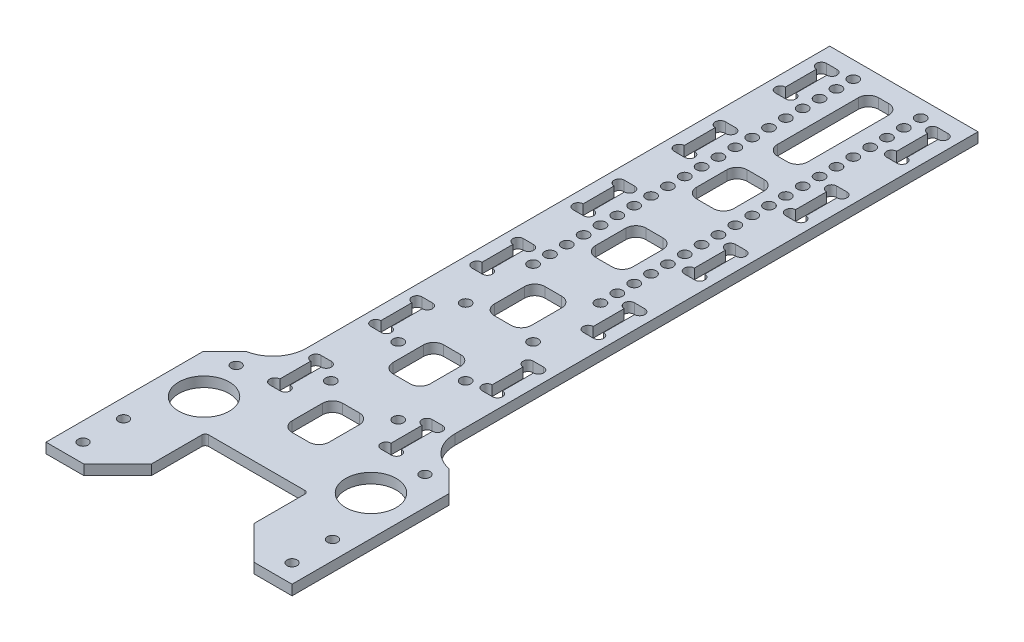
SolidWorks part; units mm, degrees
material "Thornel Mat VMA"
ref_plane "前视基准面" through (0, 0, 0) normal (0, 0, 1) x (1, 0, 0)
ref_plane "上视基准面" through (0, 0, 0) normal (0, 1, 0) x (1, 0, 0)
ref_plane "右视基准面" through (0, 0, 0) normal (1, 0, 0) x (0, 0, -1)
sketch "草图1" plane through (0, 0, 0) normal (0, 1, 0) x (1, 0, 0)
  line L1 (0, 0) -> (80, 0)
  line L2 (0, 0) -> (0, 225)
  line L3 (0, 225) -> (80, 225)
  line L4 (80, 0) -> (80, 225)
  dimension "D1" = 80
  dimension "D2" = 225
extrude "凸台-拉伸1" add sketch "草图1" along normal blind 3
sketch "草图2" plane through (0, 3, 0) normal (0, 1, 0) x (1, 0, 0)
  line L0 (40, 0) -> (40, 225) construction
  line L5 (0, 0) -> (80, 0) construction
  line L6 (80, 225) -> (0, 225) construction
  line L12 (55.25, 33) -> (24.75, 33)
  line L13 (55.25, 33) -> (55.25, 0)
  line L14 (55.25, 0) -> (24.75, 0)
  line L15 (24.75, 33) -> (24.75, 0)
  line L16 (55.25, 33) -> (24.75, 0) construction
  line L17 (55.25, 0) -> (24.75, 33) construction
  point P0 (40, 16.5)
  dimension "D1" = 33
  dimension "D2" = 30.5
extrude "切除-拉伸1" cut sketch "草图2" against normal through all
sketch "草图3" plane through (0, 0, 0) normal (0, -1, 0) x (1, 0, 0)
  line L1 (40, -225) -> (40, -33) construction
  line L2 (80, -225) -> (62, -225)
  line L3 (80, -225) -> (80, -60)
  line L4 (80, -60) -> (62, -60)
  line L5 (62, -225) -> (62, -60)
  line L6 (80, -225) -> (0, -225) construction
  line L7 (55.25, -33) -> (24.75, -33) construction
  line L8 (0, -60) -> (18, -60)
  line L9 (18, -225) -> (18, -60)
  line L10 (0, -225) -> (18, -225)
  line L11 (0, -225) -> (0, -60)
  dimension "D1" = 165
  dimension "D2" = 18
extrude "切除-拉伸2" cut sketch "草图3" against normal blind 3
chamfer "倒角1" distance 10 angle 45 2 edges at (80, 1.5, -60) (0, 1.5, -60)
fillet "圆角1" radius 10 2 edges at (62, 1.5, -60) (18, 1.5, -60)
sketch "草图4" plane through (0, 3, 0) normal (0, 1, 0) x (1, 0, 0)
  line L0 (40, 225) -> (40, 33) construction
  line L1 (62, 225) -> (18, 225) construction
  line L2 (55.25, 33) -> (24.75, 33) construction
  line L3 (18, 225) -> (18, 69.798) construction
  line L4 (21.95, 220.1) -> (25.05, 220.1)
  line L5 (21.95, 220.1) -> (21.95, 204.9)
  line L6 (21.95, 204.9) -> (25.05, 204.9)
  line L7 (25.05, 220.1) -> (25.05, 204.9)
  line L8 (58.05, 204.9) -> (54.95, 204.9)
  line L9 (54.95, 220.1) -> (54.95, 204.9)
  line L10 (58.05, 220.1) -> (54.95, 220.1)
  line L11 (58.05, 220.1) -> (58.05, 204.9)
  line L12 (21.95, 190.1) -> (21.95, 174.9)
  line L13 (21.95, 190.1) -> (25.05, 190.1)
  line L14 (25.05, 190.1) -> (25.05, 174.9)
  line L15 (21.95, 174.9) -> (25.05, 174.9)
  line L16 (58.05, 174.9) -> (54.95, 174.9)
  line L17 (54.95, 190.1) -> (54.95, 174.9)
  line L18 (58.05, 190.1) -> (54.95, 190.1)
  line L19 (58.05, 190.1) -> (58.05, 174.9)
  line L20 (21.95, 160.1) -> (21.95, 144.9)
  line L21 (21.95, 160.1) -> (25.05, 160.1)
  line L22 (25.05, 160.1) -> (25.05, 144.9)
  line L23 (21.95, 144.9) -> (25.05, 144.9)
  line L24 (58.05, 144.9) -> (54.95, 144.9)
  line L25 (54.95, 160.1) -> (54.95, 144.9)
  line L26 (58.05, 160.1) -> (54.95, 160.1)
  line L27 (58.05, 160.1) -> (58.05, 144.9)
  line L28 (21.95, 130.1) -> (21.95, 114.9)
  line L29 (21.95, 130.1) -> (25.05, 130.1)
  line L30 (25.05, 130.1) -> (25.05, 114.9)
  line L31 (21.95, 114.9) -> (25.05, 114.9)
  line L32 (58.05, 114.9) -> (54.95, 114.9)
  line L33 (54.95, 130.1) -> (54.95, 114.9)
  line L34 (58.05, 130.1) -> (54.95, 130.1)
  line L35 (58.05, 130.1) -> (58.05, 114.9)
  line L36 (21.95, 100.1) -> (21.95, 84.9)
  line L37 (21.95, 100.1) -> (25.05, 100.1)
  line L38 (25.05, 100.1) -> (25.05, 84.9)
  line L39 (21.95, 84.9) -> (25.05, 84.9)
  line L40 (58.05, 84.9) -> (54.95, 84.9)
  line L41 (54.95, 100.1) -> (54.95, 84.9)
  line L42 (58.05, 100.1) -> (54.95, 100.1)
  line L43 (58.05, 100.1) -> (58.05, 84.9)
  line L44 (21.95, 70.1) -> (21.95, 54.9)
  line L45 (21.95, 70.1) -> (25.05, 70.1)
  line L46 (25.05, 70.1) -> (25.05, 54.9)
  line L47 (21.95, 54.9) -> (25.05, 54.9)
  line L48 (58.05, 54.9) -> (54.95, 54.9)
  line L49 (54.95, 70.1) -> (54.95, 54.9)
  line L50 (58.05, 70.1) -> (54.95, 70.1)
  line L51 (58.05, 70.1) -> (58.05, 54.9)
  dimension "D1" = 4.9
  dimension "D2" = 3.95
  dimension "D3" = 3.1
  dimension "D4" = 15.2
  dimension "D5" = 6
extrude "切除-拉伸3" cut sketch "草图4" against normal through all
sketch "草图6" plane through (0, 3, 0) normal (0, 1, 0) x (1, 0, 0)
  line L1 (62, 225) -> (18, 225) construction
  circle A0 centre (50, 220) radius 1.55
  circle A1 centre (30, 220) radius 1.55
  circle A22 centre (30, 215) radius 1.55
  circle A23 centre (50, 215) radius 1.55
  circle A24 centre (30, 210) radius 1.55
  circle A25 centre (50, 210) radius 1.55
  circle A26 centre (30, 205) radius 1.55
  circle A27 centre (50, 205) radius 1.55
  circle A28 centre (30, 200) radius 1.55
  circle A29 centre (50, 200) radius 1.55
  circle A30 centre (30, 195) radius 1.55
  circle A31 centre (50, 195) radius 1.55
  circle A32 centre (30, 190) radius 1.55
  circle A33 centre (50, 190) radius 1.55
  circle A34 centre (30, 185) radius 1.55
  circle A35 centre (50, 185) radius 1.55
  circle A36 centre (30, 180) radius 1.55
  circle A37 centre (50, 180) radius 1.55
  circle A38 centre (30, 175) radius 1.55
  circle A39 centre (50, 175) radius 1.55
  circle A40 centre (30, 170) radius 1.55
  circle A41 centre (50, 170) radius 1.55
  circle A42 centre (30, 165) radius 1.55
  circle A43 centre (50, 165) radius 1.55
  circle A44 centre (30, 160) radius 1.55
  circle A45 centre (50, 160) radius 1.55
  circle A46 centre (30, 155) radius 1.55
  circle A47 centre (50, 155) radius 1.55
  circle A48 centre (30, 150) radius 1.55
  circle A49 centre (50, 150) radius 1.55
  circle A50 centre (30, 145) radius 1.55
  circle A51 centre (50, 145) radius 1.55
  circle A52 centre (30, 140) radius 1.55
  circle A53 centre (50, 140) radius 1.55
  circle A54 centre (30, 135) radius 1.55
  circle A55 centre (50, 135) radius 1.55
  circle A56 centre (30, 130) radius 1.55
  circle A57 centre (50, 130) radius 1.55
  circle A58 centre (30, 125) radius 1.55
  circle A59 centre (50, 125) radius 1.55
  circle A60 centre (30, 105) radius 1.55
  circle A61 centre (50, 105) radius 1.55
  circle A62 centre (30, 85) radius 1.55
  circle A63 centre (50, 85) radius 1.55
  circle A64 centre (30, 65) radius 1.55
  circle A65 centre (50, 65) radius 1.55
  dimension "D3" = 3.1
  dimension "D1" = 15
  dimension "D2" = 5
  dimension "D4" = 6
extrude "切除-拉伸4" cut sketch "草图6" against normal through all
sketch "草图7" plane through (0, 3, 0) normal (0, 1, 0) x (1, 0, 0)
  line L0 (40, 225) -> (40, 46) construction
  line L1 (62, 225) -> (18, 225) construction
  line L2 (34.5, 136) -> (34.5, 151)
  line L3 (35.5, 189) -> (44.5, 189)
  line L4 (35.5, 189) -> (35.5, 219)
  line L5 (35.5, 219) -> (44.5, 219)
  line L6 (44.5, 189) -> (44.5, 219)
  line L7 (35.5, 189) -> (44.5, 219) construction
  line L8 (35.5, 219) -> (44.5, 189) construction
  line L9 (34.5, 166) -> (45.5, 166)
  line L10 (34.5, 166) -> (34.5, 181)
  line L11 (34.5, 181) -> (45.5, 181)
  line L12 (45.5, 166) -> (45.5, 181)
  line L13 (34.5, 166) -> (45.5, 181) construction
  line L14 (34.5, 181) -> (45.5, 166) construction
  line L15 (34.5, 136) -> (45.5, 136)
  line L16 (45.5, 136) -> (45.5, 151)
  line L17 (34.5, 151) -> (45.5, 151)
  line L18 (34.5, 106) -> (34.5, 121)
  line L19 (34.5, 106) -> (45.5, 106)
  line L20 (45.5, 106) -> (45.5, 121)
  line L21 (34.5, 121) -> (45.5, 121)
  line L22 (34.5, 76) -> (34.5, 91)
  line L23 (34.5, 76) -> (45.5, 76)
  line L24 (45.5, 76) -> (45.5, 91)
  line L25 (34.5, 91) -> (45.5, 91)
  line L26 (34.5, 46) -> (34.5, 61)
  line L27 (34.5, 46) -> (45.5, 46)
  line L28 (45.5, 46) -> (45.5, 61)
  line L29 (34.5, 61) -> (45.5, 61)
  point P4 (40, 204)
  point P9 (40, 173.5)
  dimension "D2" = 11
  dimension "D1" = 5
extrude "切除-拉伸5" cut sketch "草图7" against normal blind 3
fillet "圆角2" radius 3 24 edges at (35.5, 1.5, -219) (44.5, 1.5, -219) (35.5, 1.5, -189) (44.5, 1.5, -189) (45.5, 1.5, -181) (34.5, 1.5, -181) (34.5, 1.5, -166) (45.5, 1.5, -166) (45.5, 1.5, -151) (34.5, 1.5, -151) (34.5, 1.5, -136) (45.5, 1.5, -136) (34.5, 1.5, -121) (34.5, 1.5, -106) (45.5, 1.5, -106) (45.5, 1.5, -121) (45.5, 1.5, -91) (34.5, 1.5, -91) (34.5, 1.5, -76) (45.5, 1.5, -76) (45.5, 1.5, -61) (34.5, 1.5, -61) (34.5, 1.5, -46) (45.5, 1.5, -46)
extrude "切除-拉伸6" cut sketch "草图8" against normal mid plane 90
sketch "草图8" plane through (-19.2821, -20, 1.5) normal (0, -1, 0) x (-1, 0, 0)
  line L0 (-59.2821, -13) -> (-59.2821, 41) construction
  circle A2 centre (-28.2821, 14) radius 1.5
  circle A3 centre (-90.2821, 14) radius 1.5
  circle A6 centre (-90.2821, 26) radius 1.5
  circle A7 centre (-28.2821, 26) radius 1.5
sketch "草图9" plane through (0, 3, 0) normal (0, 1, 0) x (1, 0, 0)
  line L0 (40, -10.932) -> (40, 56.3026) construction
  line L1 (0, 0) -> (3.5, 0)
  line L2 (0, 0) -> (0, 64.8722)
  line L3 (0, 64.8722) -> (3.5, 64.8722)
  line L4 (3.5, 7) -> (3.5, 64.8722)
  line L5 (80, 64.8722) -> (76.5, 64.8722)
  line L6 (76.5, 7) -> (76.5, 64.8722)
  line L7 (80, 0) -> (76.5, 0)
  line L8 (80, 0) -> (80, 64.8722)
  line L10 (3.5, 7) -> (76.5, 7)
  line L12 (3.5, 0) -> (76.5, 0)
  circle A0 centre (15.2377, 42.1453) radius 7.5
  circle A1 centre (64.7623, 42.1453) radius 7.5
  circle A2 centre (9, 12.5) radius 1.5 construction
  dimension "D2" = 15
  dimension "D3" = 5.5
  dimension "D1" = 3.5
extrude "切除-拉伸7" cut sketch "草图9" against normal through all
chamfer "倒角2" distance 10 angle 45 2 edges at (55.25, 1.5, -7) (24.75, 1.5, -7)
sketch "草图10" plane through (0, 3, 0) normal (0, 1, 0) x (1, 0, 0)
  line L0 (21.95, 220.1) -> (21.95, 218.6) construction
  line L1 (21.95, 220.1) -> (21.95, 204.9) construction
  line L5 (21.95, 190.1) -> (21.95, 174.9) construction
  line L9 (21.95, 160.1) -> (21.95, 144.9) construction
  line L11 (21.95, 130.1) -> (21.95, 114.9) construction
  line L13 (21.95, 100.1) -> (21.95, 84.9) construction
  line L15 (21.95, 70.1) -> (21.95, 54.9) construction
  line L17 (21.95, 54.9) -> (25.05, 54.9) construction
  line L18 (25.05, 70.1) -> (21.95, 70.1) construction
  line L19 (21.95, 84.9) -> (25.05, 84.9) construction
  line L20 (25.05, 100.1) -> (21.95, 100.1) construction
  line L21 (21.95, 114.9) -> (25.05, 114.9) construction
  line L22 (25.05, 130.1) -> (21.95, 130.1) construction
  line L23 (21.95, 144.9) -> (25.05, 144.9) construction
  line L24 (25.05, 160.1) -> (21.95, 160.1) construction
  line L25 (21.95, 174.9) -> (25.05, 174.9) construction
  line L26 (25.05, 190.1) -> (21.95, 190.1) construction
  line L27 (21.95, 204.9) -> (25.05, 204.9) construction
  line L28 (23.5, 220.1) -> (23.5, 190.1) construction
  line L29 (25.05, 220.1) -> (21.95, 220.1) construction
  line L30 (40, 219) -> (40, 189) construction
  line L31 (41.5, 219) -> (38.5, 219) construction
  line L32 (38.5, 189) -> (41.5, 189) construction
  circle A0 centre (21.95, 218.6) radius 1.5
  circle A2 centre (21.95, 206.4) radius 1.5
  circle A8 centre (21.95, 188.6) radius 1.5
  circle A15 centre (21.95, 176.4) radius 1.5
  circle A16 centre (21.95, 158.6) radius 1.5
  circle A18 centre (21.95, 146.4) radius 1.5
  circle A20 centre (21.95, 128.6) radius 1.5
  circle A22 centre (21.95, 116.4) radius 1.5
  circle A24 centre (21.95, 98.6) radius 1.5
  circle A26 centre (21.95, 86.4) radius 1.5
  circle A28 centre (21.95, 68.6) radius 1.5
  circle A30 centre (21.95, 56.4) radius 1.5
  circle A32 centre (25.05, 56.4) radius 1.5
  circle A33 centre (25.05, 68.6) radius 1.5
  circle A34 centre (25.05, 86.4) radius 1.5
  circle A35 centre (25.05, 98.6) radius 1.5
  circle A36 centre (25.05, 116.4) radius 1.5
  circle A37 centre (25.05, 128.6) radius 1.5
  circle A38 centre (25.05, 146.4) radius 1.5
  circle A39 centre (25.05, 158.6) radius 1.5
  circle A40 centre (25.05, 176.4) radius 1.5
  circle A41 centre (25.05, 188.6) radius 1.5
  circle A42 centre (25.05, 206.4) radius 1.5
  circle A43 centre (25.05, 218.6) radius 1.5
  circle A44 centre (54.95, 98.6) radius 1.5
  circle A45 centre (54.95, 86.4) radius 1.5
  circle A46 centre (54.95, 68.6) radius 1.5
  circle A47 centre (54.95, 56.4) radius 1.5
  circle A48 centre (58.05, 56.4) radius 1.5
  circle A49 centre (58.05, 68.6) radius 1.5
  circle A50 centre (58.05, 86.4) radius 1.5
  circle A51 centre (58.05, 98.6) radius 1.5
  circle A52 centre (58.05, 116.4) radius 1.5
  circle A53 centre (54.95, 116.4) radius 1.5
  circle A54 centre (54.95, 128.6) radius 1.5
  circle A55 centre (58.05, 128.6) radius 1.5
  circle A56 centre (54.95, 146.4) radius 1.5
  circle A57 centre (58.05, 146.4) radius 1.5
  circle A58 centre (54.95, 158.6) radius 1.5
  circle A59 centre (58.05, 158.6) radius 1.5
  circle A60 centre (58.05, 176.4) radius 1.5
  circle A61 centre (54.95, 176.4) radius 1.5
  circle A62 centre (54.95, 188.6) radius 1.5
  circle A63 centre (58.05, 188.6) radius 1.5
  circle A64 centre (54.95, 206.4) radius 1.5
  circle A65 centre (58.05, 206.4) radius 1.5
  circle A66 centre (58.05, 218.6) radius 1.5
  circle A67 centre (54.95, 218.6) radius 1.5
  dimension "D2" = 3
  dimension "D3" = 3
  dimension "D4" = 1.5
  dimension "D5" = 1.5
  dimension "D6" = 1.5
  dimension "D7" = 1.5
  dimension "D8" = 1.5
  dimension "D9" = 3
  dimension "D10" = 1.5
  dimension "D11" = 1.5
  dimension "D12" = 1.5
  dimension "D13" = 1.5
  dimension "D14" = 1.5
  dimension "D15" = 1.5
  dimension "D16" = 3
  dimension "D17" = 3
  dimension "D19" = 3
  dimension "D21" = 3
  dimension "D23" = 3
  dimension "D25" = 3
  dimension "D27" = 3
  dimension "D29" = 3
  dimension "D31" = 3
  dimension "D1" = 1.5
extrude "切除-拉伸8" cut sketch "草图10" against normal blind 10
sketch "草图12" plane through (0, 3, 0) normal (0, 1, 0) x (1, 0, 0)
  line L0 (40, 91) -> (40, 46) construction
  line L1 (42.5, 91) -> (37.5, 91) construction
  line L2 (37.5, 46) -> (42.5, 46) construction
  line L4 (10, 60) -> (3.5, 53.5) construction
  line L5 (76.5, 53.5) -> (70, 60) construction
  circle A0 centre (12, 54.9289) radius 1.5
  circle A1 centre (68, 54.9289) radius 1.5
  dimension "D1" = 3
  dimension "D2" = 3
  dimension "D3" = 28
  dimension "D4" = 28
  dimension "D5" = 5
  dimension "D6" = 5
extrude "切除-拉伸9" cut sketch "草图12" against normal blind 10
fillet "圆角3" radius 1 2 edges at (55.25, 1.5, -33) (24.75, 1.5, -33)
